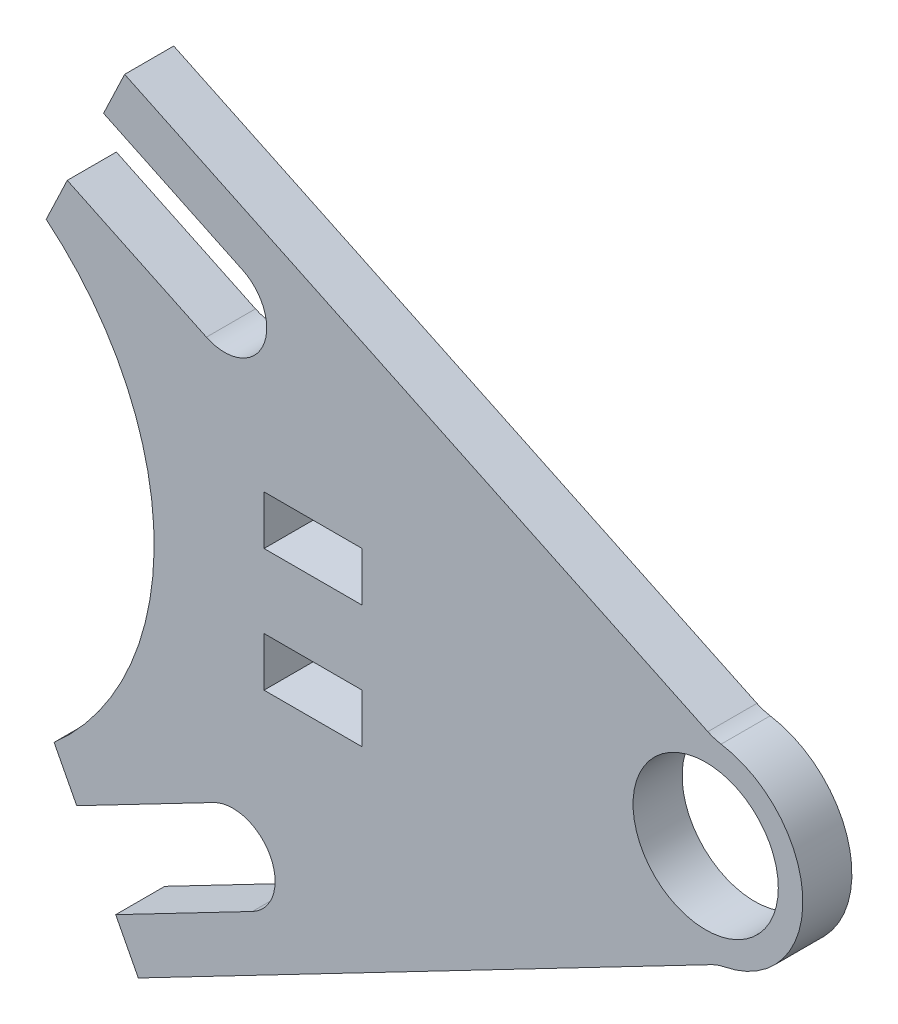
SolidWorks part; units mm, degrees
ref_plane "Front" through (0, 0, 0) normal (0, 0, 1) x (1, 0, 0)
ref_plane "Top" through (0, 0, 0) normal (0, 1, 0) x (1, 0, 0)
ref_plane "Right" through (0, 0, 0) normal (1, 0, 0) x (0, 0, -1)
sketch "Sketch1" plane through (0, 0, 0) normal (0, 0, 1) x (1, 0, 0)
  line L0 (581.3633, -1568.0737) -> (524.0316, -1540.7729) construction
  line L1 (275.4478, -1422.4) -> (581.3633, -1568.0737) construction
  line L2 (581.3633, -1568.0737) -> (525.0288, -1597.3769) construction
  line L3 (581.3633, -1568.0737) -> (275.4478, -1727.2) construction
  line L4 (521.4489, -1533.4945) -> (503.4468, -1524.9221)
  line L5 (516.7532, -1543.3556) -> (498.7511, -1534.7832)
  line L6 (498.7511, -1534.7832) -> (496.021, -1540.5163)
  line L7 (496.021, -1540.5163) -> (572.3935, -1576.8841)
  line L8 (503.4468, -1524.9221) -> (506.1769, -1519.189)
  line L9 (506.1769, -1519.189) -> (582.5494, -1555.5567)
  line L10 (517.6639, -1595.0522) -> (499.9749, -1604.2534)
  line L11 (522.7041, -1604.7417) -> (505.0151, -1613.9429)
  line L12 (517.6639, -1595.0522) -> (520.184, -1599.8969)
  line L13 (520.184, -1599.8969) -> (522.7041, -1604.7417)
  line L14 (499.9749, -1604.2534) -> (497.0446, -1598.6199)
  line L15 (497.0446, -1598.6199) -> (572.0888, -1559.5846)
  line L16 (505.0151, -1613.9429) -> (507.9454, -1619.5763)
  line L17 (507.9454, -1619.5763) -> (582.9895, -1580.541)
  circle A0 centre (581.3633, -1568.0737) radius 9.398
  circle A1 centre (581.3633, -1568.0737) radius 12.573
  arc A2 (521.4489, -1533.4945) -> (516.7532, -1543.3556) centre (519.1011, -1538.4251) cw
  arc A3 (517.6639, -1595.0522) -> (522.7041, -1604.7417) centre (520.184, -1599.8969) cw
  point P14 (524.0316, -1540.7729)
  point P24 (525.0288, -1597.3769)
  dimension "D1" = 18.796
  dimension "D2" = 3.175
  dimension "D3" = 25.4
  dimension "D4" = 63.5
  dimension "D5" = 6.35
  dimension "D6" = 11.811
extrude "Boss-Extrude1" add sketch "Sketch1" along normal mid plane 6.35 contours L4 A2 L5 L6 L7 L15 A1 L9 L8 | A1 L15 L7 | L10 A3 L11 L16 L17 A1 L7 L15 L14 | A1 A0 region at (538.8996, -1547.2501, 0) region at (590.4006, -1559.8523, 0) region at (564.8019, -1568.3654, 0) region at (539.6594, -1590.3801, 0)
fillet "Fillet1" radius 38.1 1 edges at (554.8716, -1568.5404, 0)
fillet "Fillet2" radius 6.35 2 edges at (582.5494, -1555.5567, 0) (582.9895, -1580.541, 0)
sketch "Sketch2" plane through (0, 0, 0) normal (0, 0, 1) x (1, 0, 0)
  line L0 (581.3633, -1568.0737) -> (530.5633, -1568.0737) construction
  line L1 (530.5633, -1563.3112) -> (530.5633, -1572.8362) construction
  line L2 (536.9133, -1563.3112) -> (524.2133, -1563.3112)
  line L3 (536.9133, -1572.8362) -> (524.2133, -1572.8362)
  line L4 (524.2133, -1563.3112) -> (524.2133, -1556.9612)
  line L5 (524.2133, -1556.9612) -> (536.9133, -1556.9612)
  line L6 (536.9133, -1556.9612) -> (536.9133, -1563.3112)
  line L7 (524.2133, -1572.8362) -> (524.2133, -1579.1862)
  line L8 (524.2133, -1579.1862) -> (536.9133, -1579.1862)
  line L9 (536.9133, -1579.1862) -> (536.9133, -1572.8362)
  point P7 (530.5633, -1568.0737)
  point P10 (530.5633, -1563.3112)
  point P13 (530.5633, -1572.8362)
  dimension "D1" = 6.35
  dimension "D2" = 12.7
  dimension "D3" = 9.525
extrude "Cut-Extrude1" cut sketch "Sketch2" against normal mid plane 6.35
equation "\"D6@Sketch1\"=0.465"
